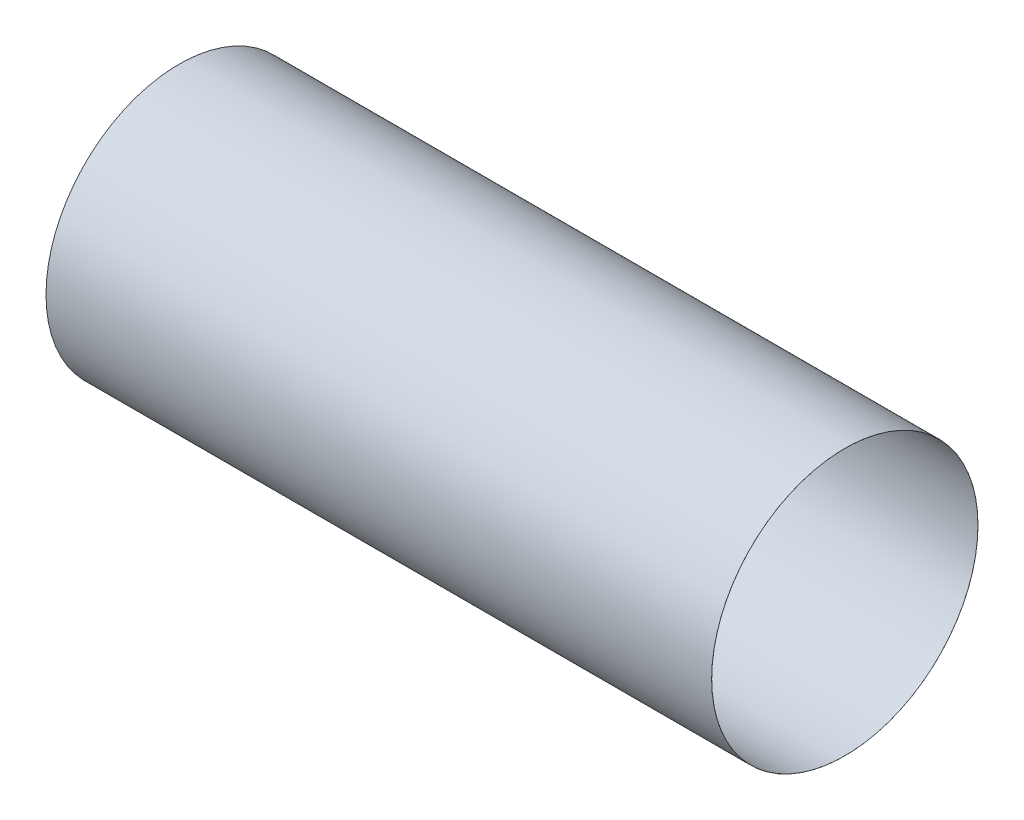
SolidWorks part; units mm, degrees
material "Air"
ref_plane "Front" through (0, 0, 0) normal (0, 0, 1) x (1, 0, 0)
ref_plane "Top" through (0, 0, 0) normal (0, 1, 0) x (1, 0, 0)
ref_plane "Right" through (0, 0, 0) normal (1, 0, 0) x (0, 0, -1)
sketch "Sketch2" plane through (0, 0, 0) normal (1, 0, 0) x (0, 0, -1)
  circle A0 centre (0, 0) radius 60.96
  dimension "D1" = 121.92
extrude "Extrude-Thin1" add sketch "Sketch2" along normal blind 304.8 thin thin type one direction wall 0.0254
